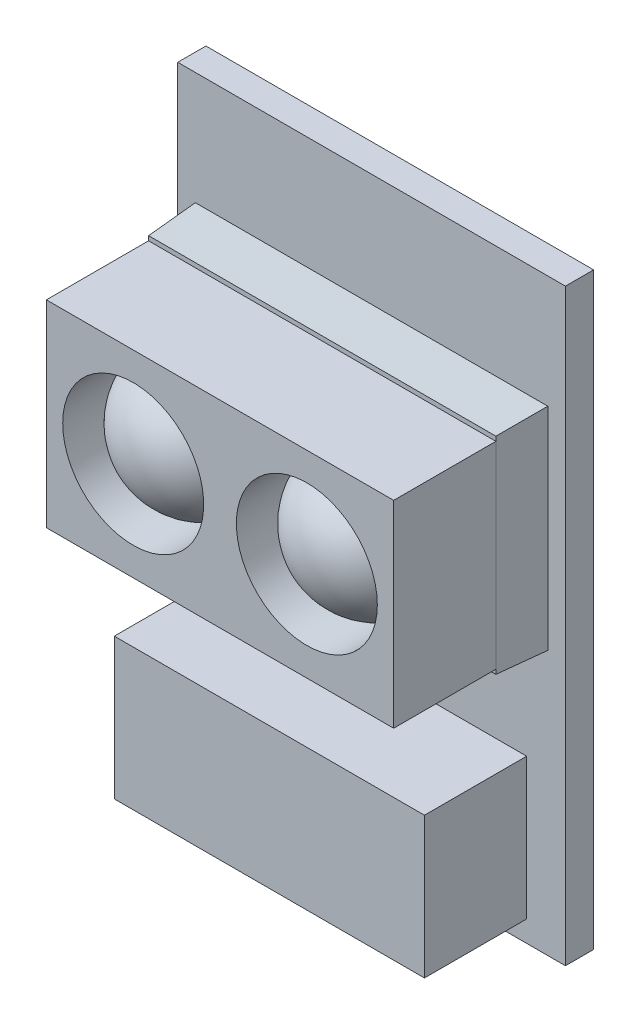
SolidWorks part; units mm, degrees
ref_plane "Front Plane" through (0, 0, 0) normal (0, 0, 1) x (1, 0, 0)
ref_plane "Top Plane" through (0, 0, 0) normal (0, 1, 0) x (1, 0, 0)
ref_plane "Right Plane" through (0, 0, 0) normal (1, 0, 0) x (0, 0, -1)
sketch "Sketch1" plane through (0, 0, 0) normal (0, 0, 1) x (1, 0, 0)
  line L1 (-5.5, -8.35) -> (5.5, -8.35)
  line L2 (-5.5, -8.35) -> (-5.5, 8.35)
  line L3 (-5.5, 8.35) -> (5.5, 8.35)
  line L4 (5.5, -8.35) -> (5.5, 8.35)
  line L5 (-5.5, -8.35) -> (5.5, 8.35) construction
  line L6 (-5.5, 8.35) -> (5.5, -8.35) construction
  point P0 (0, 0)
  dimension "D1" = 16.7
  dimension "D2" = 11
extrude "PCB" add sketch "Sketch1" along normal blind 0.8
sketch "Sketch3" plane through (0, 0, 0.8) normal (0, 0, 1) x (1, 0, 0)
  line L0 (-5.5, -8.35) -> (5.5, -8.35) construction
  line L1 (5, -0.85) -> (-5, -0.85)
  line L2 (5, -0.85) -> (5, 5.15)
  line L3 (5, 5.15) -> (-5, 5.15)
  line L4 (-5, -0.85) -> (-5, 5.15)
  line L5 (5, -0.85) -> (-5, 5.15) construction
  line L6 (5, 5.15) -> (-5, -0.85) construction
  point P0 (0, 2.15)
  dimension "D1" = 6
  dimension "D2" = 10
  dimension "D3" = 10.5
extrude "Boss-Extrude3" add sketch "Sketch3" along normal blind 1.4 draft 3
sketch "Sketch4" plane through (0, 0, 2.2) normal (0, 0, 1) x (1, 0, 0)
  line L0 (0, -0.7766) -> (0, 5.0766) construction
  line L1 (-4.9266, -0.7766) -> (4.9266, -0.7766) construction
  line L2 (4.9266, 5.0766) -> (-4.9266, 5.0766) construction
  line L3 (-4.9266, 2.15) -> (4.9266, 2.15) construction
  line L4 (-4.9266, 5.0766) -> (-4.9266, -0.7766) construction
  line L5 (4.9266, -0.7766) -> (4.9266, 5.0766) construction
  line L7 (-4.9266, -0.65) -> (4.9266, -0.65)
  line L8 (-4.9266, -0.65) -> (-4.9266, 4.95)
  line L9 (-4.9266, 4.95) -> (4.9266, 4.95)
  line L10 (4.9266, -0.65) -> (4.9266, 4.95)
  line L11 (-4.9266, -0.65) -> (4.9266, 4.95) construction
  line L12 (-4.9266, 4.95) -> (4.9266, -0.65) construction
  point P12 (0, 2.15)
  dimension "D1" = 5.6
extrude "Boss-Extrude4" add sketch "Sketch4" along normal blind 2.9
sketch "Sketch5" plane through (0, 0, 5.1) normal (0, 0, 1) x (1, 0, 0)
  line L0 (0, -0.65) -> (0, 4.95) construction
  line L1 (-4.9266, -0.65) -> (4.9266, -0.65) construction
  line L2 (4.9266, 4.95) -> (-4.9266, 4.95) construction
  line L3 (4.9266, -0.65) -> (4.9266, 4.95) construction
  line L4 (0, 4.95) -> (4.9266, 4.95) construction
  circle A0 centre (2.4633, 2.15) radius 2
  circle A1 centre (-2.4633, 2.15) radius 2
  point P13 (4.9266, 2.15)
  point P14 (2.4633, 4.95)
  dimension "D1" = 4
extrude "Cut-Extrude1" cut sketch "Sketch5" against normal blind 2 contours A1 | A0
sketch "Sketch6" plane through (0, 0, 3.1) normal (0, 0, 1) x (1, 0, 0)
  line L0 (0, -2.805) -> (0, 2.805) construction
  circle A0 centre (2.4633, 2.15) radius 1.75
  circle A1 centre (-2.4633, 2.15) radius 1.75
  dimension "D1" = 3.5
dome "Dome1" faces to dome 1 distance 2 reverse direction no elliptical dome no face at (4.4633, 2.15, 3.1) parameters "D1"=2
dome "Dome2" faces to dome 1 distance 2 reverse direction no elliptical dome no face at (-4.4633, 2.15, 3.1) parameters "D1"=2
sketch "Sketch7" plane through (0, 0, 0.8) normal (0, 0, 1) x (1, 0, 0)
  line L1 (4.4, -7.75) -> (-4.4, -7.75)
  line L2 (4.4, -7.75) -> (4.4, -3.75)
  line L3 (4.4, -3.75) -> (-4.4, -3.75)
  line L4 (-4.4, -7.75) -> (-4.4, -3.75)
  line L5 (4.4, -7.75) -> (-4.4, -3.75) construction
  line L6 (4.4, -3.75) -> (-4.4, -7.75) construction
  line L7 (5.5, -8.35) -> (5.5, 8.35) construction
  line L8 (-5.5, -8.35) -> (5.5, -8.35) construction
  point P0 (0, -5.75)
  dimension "D1" = 1.1
  dimension "D2" = 0.6
  dimension "D3" = 4
extrude "Boss-Extrude5" add sketch "Sketch7" along normal blind 2.9 separate body
shell "Shell1" thickness 0.2 removed face at (0, -7.75, 2.25)
